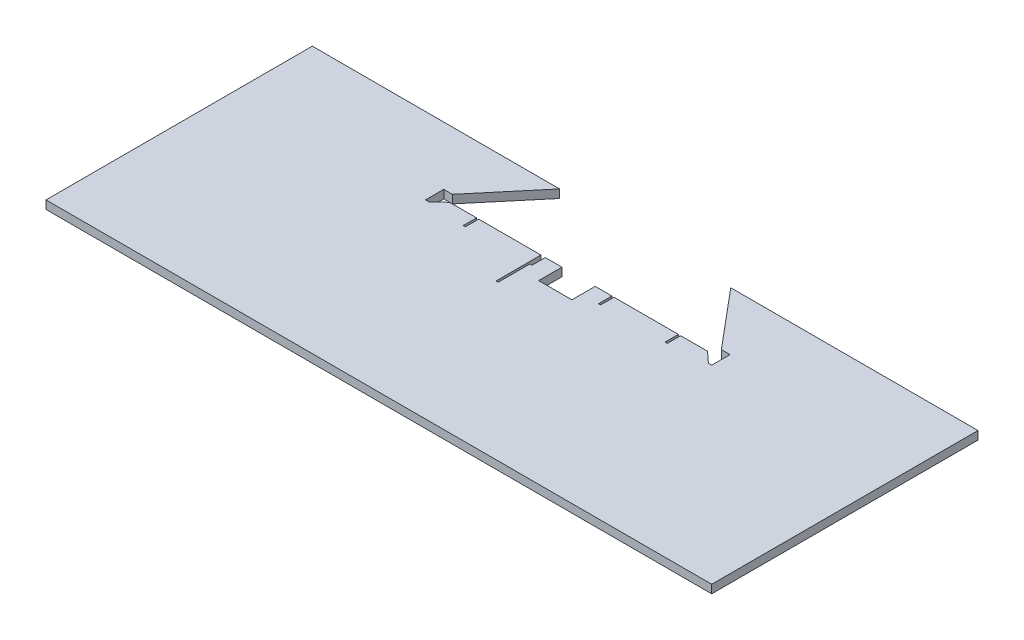
SolidWorks part; units mm, degrees
material "Depron"
ref_plane "Front Plane" through (0, 0, 0) normal (0, 0, 1) x (1, 0, 0)
ref_plane "Top Plane" through (0, 0, 0) normal (0, 1, 0) x (1, 0, 0)
ref_plane "Right Plane" through (0, 0, 0) normal (1, 0, 0) x (0, 0, -1)
sketch "Sketch1" plane through (0, 0, 0) normal (0, 1, 0) x (1, 0, 0)
  line L0 (32.6619, 101.6) -> (127, 101.6)
  line L1 (-127, 0) -> (127, 0)
  line L2 (-127, 0) -> (-127, 101.6)
  line L3 (-127, 101.6) -> (-32.6619, 101.6)
  line L4 (127, 0) -> (127, 101.6)
  line L5 (0, -898.4) -> (0, 49101.6) construction
  line L6 (-53.975, 76.2) -> (-32.6619, 101.6)
  line L7 (-53.975, 76.2) -> (53.975, 76.2)
  line L8 (53.975, 76.2) -> (32.6619, 101.6)
  line L9 (-1003.9539, 76.2) -> (48996.0461, 76.2) construction
  point P11 (0, 76.2)
  dimension "D1" = 101.6
  dimension "D2" = 254
  dimension "D4" = 107.95
  dimension "D6" = 25.4
extrude "Boss-Extrude1" add sketch "Sketch1" along normal blind 3.175
sketch "Sketch2" plane through (0, 3.175, 0) normal (0, 1, 0) x (-1, 0, 0)
  line L0 (0, 0) -> (0, -134.62) construction
  line L1 (127, 0) -> (-127, 0) construction
  line L2 (-53.975, -76.2) -> (53.975, -76.2) construction
  line L3 (38.9255, -76.2) -> (38.1, -76.2)
  line L4 (38.9255, -76.2) -> (38.9255, -71.12)
  line L5 (38.9255, -71.12) -> (38.1, -71.12)
  line L6 (38.1, -76.2) -> (38.1, -71.12)
  line L7 (13.5255, -76.2) -> (12.7, -76.2)
  line L8 (-53.975, -76.2) -> (53.975, -76.2) construction
  line L9 (13.5255, -71.12) -> (12.7, -71.12)
  line L10 (12.7, -76.2) -> (12.7, -71.12)
  line L11 (-12.7, -76.2) -> (-12.7, -71.12)
  line L12 (-13.5255, -71.12) -> (-12.7, -71.12)
  line L13 (-13.5255, -76.2) -> (-13.5255, -71.12)
  line L14 (-13.5255, -76.2) -> (-12.7, -76.2)
  line L15 (-38.1, -76.2) -> (-38.1, -71.12)
  line L16 (-38.9255, -71.12) -> (-38.1, -71.12)
  line L17 (-38.9255, -76.2) -> (-38.9255, -71.12)
  line L18 (-38.9255, -76.2) -> (-38.1, -76.2)
  line L19 (6.35, -76.2) -> (-6.35, -76.2)
  line L20 (13.5255, -76.2) -> (14.351, -76.2)
  line L21 (13.5255, -71.12) -> (13.5255, -59.055)
  line L22 (13.5255, -59.055) -> (14.351, -59.055)
  line L23 (14.351, -76.2) -> (14.351, -59.055)
  line L24 (6.35, -76.2) -> (6.35, -67.31)
  line L25 (6.35, -67.31) -> (-6.35, -67.31)
  line L26 (-6.35, -76.2) -> (-6.35, -67.31)
  line L27 (-53.975, -76.2) -> (-51.3109, -79.375)
  line L28 (53.34, -80.01) -> (54.61, -80.01) construction
  line L29 (53.34, -80.01) -> (53.34, -72.39) construction
  line L30 (53.34, -72.39) -> (54.61, -72.39)
  line L31 (54.61, -80.01) -> (54.61, -72.39) construction
  line L32 (53.34, -80.01) -> (54.61, -72.39) construction
  line L33 (53.34, -72.39) -> (54.61, -80.01) construction
  line L34 (-53.34, -76.2) -> (-53.975, -76.2)
  line L35 (-53.34, -72.39) -> (-49.1905, -76.2)
  line L36 (-53.34, -72.39) -> (-54.61, -72.39)
  line L37 (53.975, -76.2) -> (32.6619, -101.6) construction
  line L38 (53.975, -76.2) -> (51.3109, -79.375)
  line L39 (51.3109, -79.375) -> (54.61, -79.375)
  line L40 (54.61, -79.375) -> (54.61, -72.39)
  line L41 (53.34, -72.39) -> (49.1905, -76.2)
  line L42 (53.34, -76.2) -> (53.975, -76.2)
  line L43 (-54.61, -79.375) -> (-54.61, -72.39)
  line L44 (-51.3109, -79.375) -> (-54.61, -79.375)
  point P31 (0, -67.31)
  point P32 (53.975, -76.2)
  line M6 (-53.975, -76.2) -> (53.975, -76.2)
  line M38 (-32.6619, -101.6) -> (-53.975, -76.2)
  line M39 (53.975, -76.2) -> (32.6619, -101.6)
  dimension "D1" = 0.8255
  dimension "D2" = 5.08
  dimension "D4" = 5.08
  dimension "D6" = 17.145
  dimension "D7" = 12.7
  dimension "D8" = 38.1
  dimension "D9" = 12.7
  dimension "D10" = 8.89
  dimension "D11" = 1.27
  dimension "D12" = 7.62
  dimension "D13" = 3.175
  dimension "D14" = 4.7845
ref_plane "Center Plane" through (0, 0, 0) normal (1, 0, 0) x (0, 0, -1)
sketch "Sketch3" plane through (0, 3.175, 0) normal (0, 1, 0) x (1, 0, 0)
  line L0 (-38.5128, 71.12) -> (-38.5128, 76.2)
  line L1 (-38.9255, 71.12) -> (-38.1, 71.12) construction
  line L2 (-38.9255, 76.2) -> (-38.1, 76.2) construction
  line L3 (-13.9383, 76.2) -> (-13.9383, 59.055)
  line L4 (-13.5255, 76.2) -> (-14.351, 76.2) construction
  line L5 (-13.5255, 59.055) -> (-14.351, 59.055) construction
  line L6 (-13.1128, 71.12) -> (-13.1128, 76.2)
  line L7 (-13.5255, 71.12) -> (-12.7, 71.12) construction
  line L8 (-13.5255, 76.2) -> (-12.7, 76.2) construction
  line L9 (-6.35, 76.2) -> (-6.35, 67.31)
  line L10 (-6.35, 67.31) -> (6.35, 67.31)
  line L11 (6.35, 67.31) -> (6.35, 76.2)
  line L12 (13.1127, 71.12) -> (13.1127, 76.2)
  line L13 (13.5255, 71.12) -> (12.7, 71.12) construction
  line L14 (13.5255, 76.2) -> (12.7, 76.2) construction
  line L15 (38.5127, 71.12) -> (38.5127, 76.2)
  line L16 (38.9255, 71.12) -> (38.1, 71.12) construction
  line L17 (38.9255, 76.2) -> (38.1, 76.2) construction
extrude "Cuts for mouting parts" cut sketch "Sketch2" against normal up to surface (3.175 mm away) contours L6 L4 L5 M6 | L23 L22 L21 L9 L10 M6 | L26 L24 L25 M6 | L13 L11 L12 M6 | L17 L15 L16 M6 | L39 L40 L30 M6 M39 | L44 L36 L43 M38 M6 region at (52.9708, 3.175, -75.8259) region at (38.5127, 3.175, -73.66) region at (13.1127, 3.175, -73.66) region at (0, 3.175, -71.755) region at (-13.7496, 3.175, -69.0064) region at (-38.5128, 3.175, -73.66) region at (-52.9708, 3.175, -75.8259) up to face at (0, 0, -69.85)
